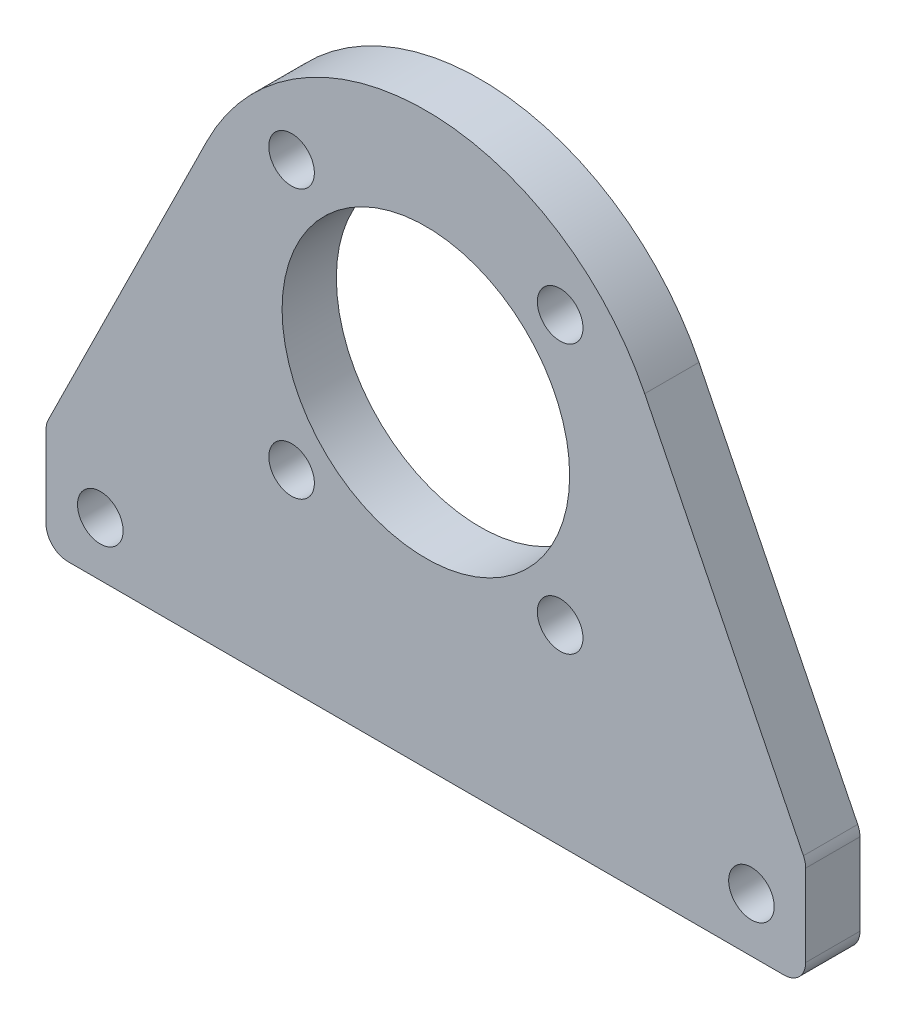
SolidWorks part; units mm, degrees
material "5052-H34"
ref_plane "正面" through (0, 0, 0) normal (0, 0, 1) x (1, 0, 0)
ref_plane "平面" through (0, 0, 0) normal (0, 1, 0) x (1, 0, 0)
ref_plane "右側面" through (0, 0, 0) normal (1, 0, 0) x (0, 0, -1)
sketch "ｽｹｯﾁ1" plane through (0, 0, 0) normal (0, 0, 1) x (1, 0, 0)
  line L0 (0, 0) -> (0, -90) construction
  line L1 (0, 0) -> (0, -115) construction
  line L2 (-12.3744, -77.6256) -> (12.3744, -77.6256) construction
  line L3 (-12.3744, -77.6256) -> (-12.3744, -102.3744) construction
  line L4 (-12.3744, -102.3744) -> (12.3744, -102.3744) construction
  line L5 (12.3744, -77.6256) -> (12.3744, -102.3744) construction
  line L6 (-12.3744, -77.6256) -> (12.3744, -102.3744) construction
  line L7 (-12.3744, -102.3744) -> (12.3744, -77.6256) construction
  line L8 (0, -115) -> (30, -115) construction
  line L9 (-35, -110) -> (-20.1663, -80.0215)
  line L11 (-35, -110) -> (-35, -120)
  line L12 (-35, -120) -> (35, -120)
  line L13 (35, -110) -> (35, -120)
  line L14 (-35, -110) -> (35, -120) construction
  line L15 (-35, -120) -> (35, -110) construction
  line L16 (35, -110) -> (20.1663, -80.0215)
  circle A0 centre (0, 0) radius 70 construction
  circle A1 centre (0, -90) radius 20 construction
  circle A2 centre (12.3744, -77.6256) radius 2.1
  circle A3 centre (12.3744, -102.3744) radius 2.1
  circle A4 centre (-12.3744, -102.3744) radius 2.1
  circle A5 centre (-12.3744, -77.6256) radius 2.1
  circle A6 centre (30, -115) radius 2.1
  circle A7 centre (-30, -115) radius 2.1
  circle A8 centre (0, -90) radius 13.25
  arc A9 (20.1663, -80.0215) -> (-20.1663, -80.0215) centre (0, -90) ccw
  point P18 (0, -90)
  dimension "D1" = 140
  dimension "D2" = 40
  dimension "D4" = 4.2
  dimension "D7" = 4.2
  dimension "D11" = 26.5
  dimension "D12" = 45
  dimension "D3" = 35
  dimension "D6" = 115
  dimension "D8" = 60
  dimension "D9" = 5
  dimension "D10" = 10
  dimension "D5" = 4
extrude "ﾎﾞｽ - 押し出し1" add sketch "ｽｹｯﾁ1" along normal blind 5
sketch "ｽｹｯﾁ2" plane through (0, 0, 5) normal (0, 0, 1) x (1, 0, 0)
  line L5 (-35, -110) -> (35, -110)
  line L6 (-35, -110) -> (35, -110)
  line L11 (-11.2035, -84.4564) -> (-26.0372, -114.4349)
  line L12 (-11.2035, -84.4564) -> (-26.0372, -114.4349)
  line L14 (26.0372, -114.4349) -> (11.2035, -84.4564)
  line L15 (26.0372, -114.4349) -> (11.2035, -84.4564)
  circle A0 centre (0, -90) radius 13.25 construction
  circle A1 centre (0, -90) radius 13.25
  circle A2 centre (0, -90) radius 22.5
  arc A3 (20.1663, -80.0215) -> (-20.1663, -80.0215) centre (0, -90) ccw construction
  dimension "D1" = 10
  dimension "D2" = 10
  dimension "D3" = 10
extrude "ｶｯﾄ - 押し出し1" [suppressed] cut sketch "ｽｹｯﾁ2" against normal through all contours A2 L12 L6 L15
fillet "ﾌｨﾚｯﾄ1" radius 2 4 edges at (35, -110, 2.5) (35, -120, 2.5) (-35, -110, 2.5) (-35, -120, 2.5)
fillet "ﾌｨﾚｯﾄ2" [suppressed] radius 5
